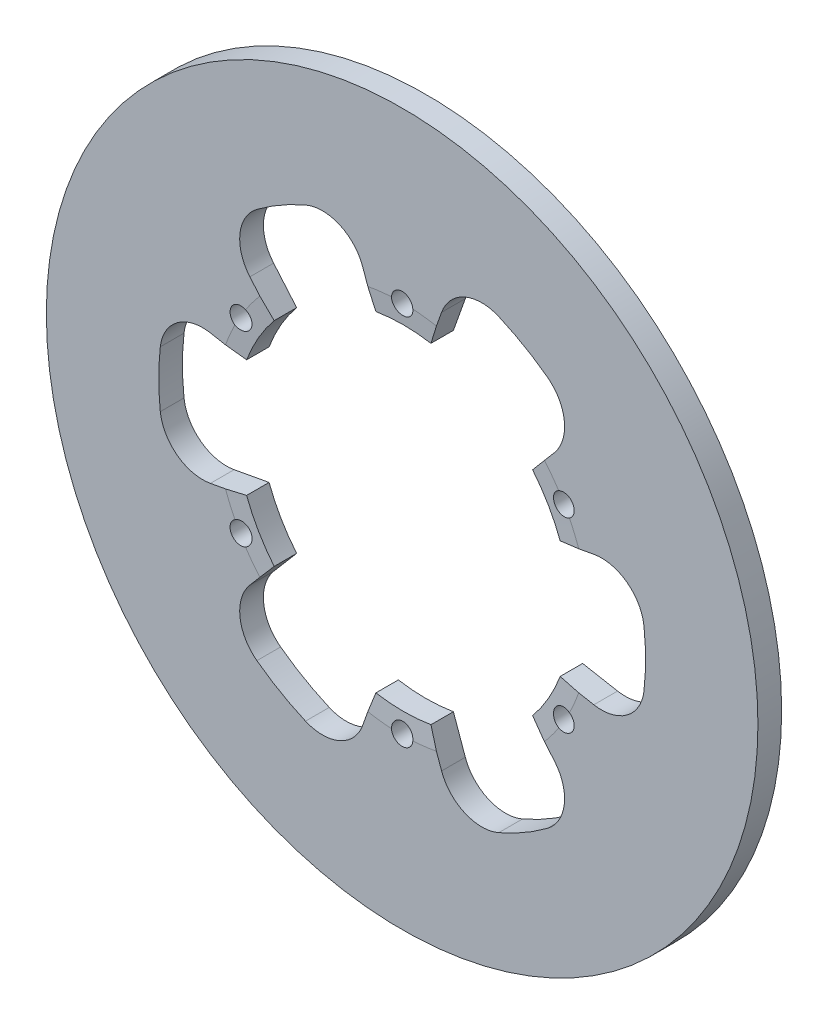
SolidWorks part; units mm, degrees
material "AISI 1020 Steel, Cold Rolled"
ref_plane "Front Plane" through (0, 0, 0) normal (0, 0, 1) x (1, 0, 0)
ref_plane "Top Plane" through (0, 0, 0) normal (0, 1, 0) x (1, 0, 0)
ref_plane "Right Plane" through (0, 0, 0) normal (1, 0, 0) x (0, 0, -1)
sketch "Sketch1" plane through (0, 0, 0) normal (0, 0, 1) x (1, 0, 0)
  line L0 (0, 0) -> (0, 133.35) construction
  line L1 (0, 0) -> (45.625, 79.0248) construction
  line L2 (14.7854, 74.4309) -> (10.3245, 61.8826)
  line L3 (57.0663, 50.0199) -> (48.4297, 39.8826)
  line L4 (10.3245, 61.8826) -> (48.4297, 39.8826) construction
  line L5 (0, 0) -> (60.4919, 34.925) construction
  line L6 (71.8517, 24.4109) -> (58.7542, 22)
  line L7 (71.8517, -24.4109) -> (58.7542, -22)
  line L8 (57.0663, -50.0199) -> (48.4297, -39.8826)
  line L9 (14.7854, -74.4309) -> (10.3245, -61.8826)
  line L10 (-14.7854, -74.4309) -> (-10.3245, -61.8826)
  line L11 (-57.0663, -50.0199) -> (-48.4297, -39.8826)
  line L12 (-71.8517, -24.4109) -> (-58.7542, -22)
  line L13 (-71.8517, 24.4109) -> (-58.7542, 22)
  line L14 (-57.0663, 50.0199) -> (-48.4297, 39.8826)
  line L15 (-14.7854, 74.4309) -> (-10.3245, 61.8826)
  circle A0 centre (0, 0) radius 133.35
  circle A1 centre (0, 0) radius 69.85 construction
  arc A2 (54.3327, 31.369) -> (48.4297, 39.8826) centre (0, 0) ccw
  circle A3 centre (0, 0) radius 91.25 construction
  circle A4 centre (0, 69.85) radius 4
  circle A5 centre (60.4919, 34.925) radius 4
  circle A6 centre (60.4919, -34.925) radius 4
  circle A7 centre (0, -69.85) radius 4
  circle A8 centre (-60.4919, -34.925) radius 4
  circle A9 centre (-60.4919, 34.925) radius 4
  circle A10 centre (0, 0) radius 11 construction
  arc A11 (36.2103, 83.7578) -> (54.4313, 73.238) centre (0, 0) cw
  arc A12 (54.4313, 73.238) -> (57.0663, 50.0199) centre (44.8872, 60.3962) cw
  arc A13 (14.7854, 74.4309) -> (36.2103, 83.7578) centre (29.8611, 69.0715) cw
  arc A14 (10.3245, 61.8826) -> (0, 62.738) centre (0, 0) ccw
  arc A15 (58.7542, 22) -> (54.3327, 31.369) centre (0, 0) ccw
  arc A16 (71.8517, 24.4109) -> (90.6416, 10.5199) centre (74.7483, 8.6753) cw
  arc A17 (90.6416, 10.5199) -> (90.6416, -10.5199) centre (0, 0) cw
  arc A18 (90.6416, -10.5199) -> (71.8517, -24.4109) centre (74.7483, -8.6753) cw
  arc A19 (54.3327, -31.369) -> (58.7542, -22) centre (0, 0) ccw
  arc A20 (48.4297, -39.8826) -> (54.3327, -31.369) centre (0, 0) ccw
  arc A21 (57.0663, -50.0199) -> (54.4313, -73.238) centre (44.8872, -60.3962) cw
  arc A22 (54.4313, -73.238) -> (36.2103, -83.7578) centre (0, 0) cw
  arc A23 (36.2103, -83.7578) -> (14.7854, -74.4309) centre (29.8611, -69.0715) cw
  arc A24 (0, -62.738) -> (10.3245, -61.8826) centre (0, 0) ccw
  arc A25 (-10.3245, -61.8826) -> (0, -62.738) centre (0, 0) ccw
  arc A26 (-14.7854, -74.4309) -> (-36.2103, -83.7578) centre (-29.8611, -69.0715) cw
  arc A27 (-36.2103, -83.7578) -> (-54.4313, -73.238) centre (0, 0) cw
  arc A28 (-54.4313, -73.238) -> (-57.0663, -50.0199) centre (-44.8872, -60.3962) cw
  arc A29 (-54.3327, -31.369) -> (-48.4297, -39.8826) centre (0, 0) ccw
  arc A30 (-58.7542, -22) -> (-54.3327, -31.369) centre (0, 0) ccw
  arc A31 (-71.8517, -24.4109) -> (-90.6416, -10.5199) centre (-74.7483, -8.6753) cw
  arc A32 (-90.6416, -10.5199) -> (-90.6416, 10.5199) centre (0, 0) cw
  arc A33 (-90.6416, 10.5199) -> (-71.8517, 24.4109) centre (-74.7483, 8.6753) cw
  arc A34 (-54.3327, 31.369) -> (-58.7542, 22) centre (0, 0) ccw
  arc A35 (-48.4297, 39.8826) -> (-54.3327, 31.369) centre (0, 0) ccw
  arc A36 (-57.0663, 50.0199) -> (-54.4313, 73.238) centre (-44.8872, 60.3962) cw
  arc A37 (-54.4313, 73.238) -> (-36.2103, 83.7578) centre (0, 0) cw
  arc A38 (-36.2103, 83.7578) -> (-14.7854, 74.4309) centre (-29.8611, 69.0715) cw
  arc A39 (0, 62.738) -> (-10.3245, 61.8826) centre (0, 0) ccw
  point P20 (0, 0)
  point P28 (67.1189, 61.8192)
  point P31 (19.9775, 89.0363)
  point P32 (29.3771, 50.8826)
  point P87 (0, 0)
  dimension "D1" = 266.7
  dimension "D2" = 139.7
  dimension "D3" = 125.476
  dimension "D4" = 42.1
  dimension "D5" = 8
  dimension "D6" = 6
  dimension "D10" = 22
  dimension "D7" = 30
  dimension "D9" = 44
extrude "Boss-Extrude1" add sketch "Sketch1" along normal blind 4.445 and the other way blind 4.445
sketch "Sketch2" plane through (0, 0, 0) normal (1, 0, 0) x (0, 0, -1)
  line L0 (-33.8318, 0) -> (32.4098, 0) construction
  line L5 (0, 0) -> (-8.445, 133.35)
  line L6 (-8.445, 133.35) -> (-26.5574, 133.35)
  line L7 (-26.5574, 133.35) -> (-26.5574, 0)
  line L8 (-26.5574, 0) -> (0, 0)
  dimension "D2" = 4
revolve "Cut-Revolve1" cut sketch "Sketch2" angle 360 about L0
